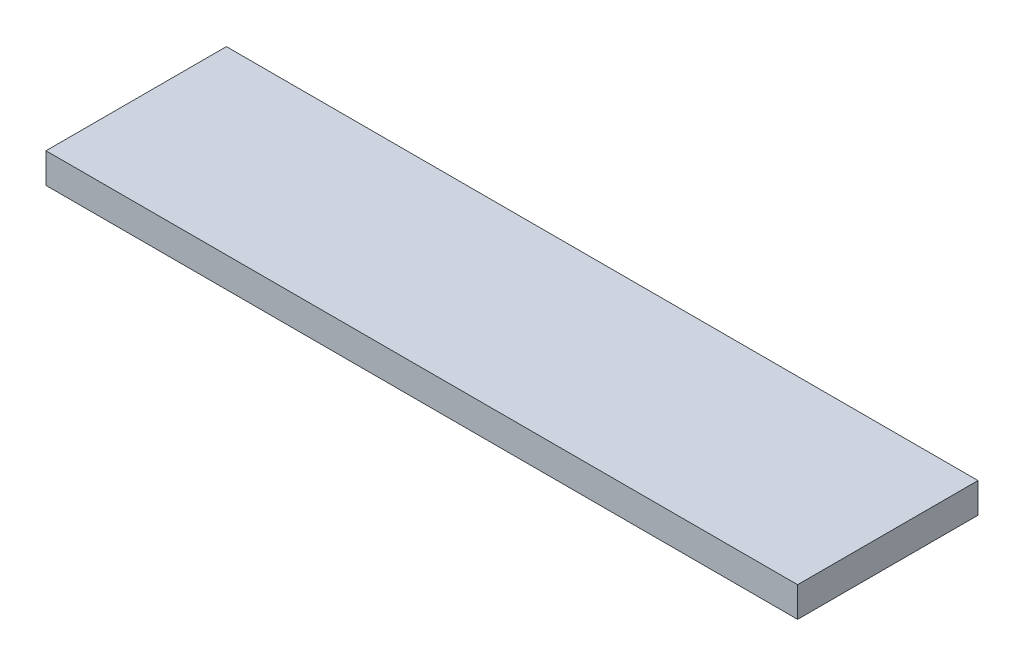
SolidWorks part; units mm, degrees
ref_plane "Front Plane" through (0, 0, 0) normal (0, 0, 1) x (1, 0, 0)
ref_plane "Top Plane" through (0, 0, 0) normal (0, 1, 0) x (1, 0, 0)
ref_plane "Right Plane" through (0, 0, 0) normal (1, 0, 0) x (0, 0, -1)
sketch "Sketch1" plane through (0, 0, 0) normal (0, 1, 0) x (1, 0, 0)
  line L1 (-62.5, 15) -> (62.5, 15)
  line L2 (-62.5, 15) -> (-62.5, -15)
  line L3 (-62.5, -15) -> (62.5, -15)
  line L4 (62.5, 15) -> (62.5, -15)
  line L5 (-62.5, 15) -> (62.5, -15) construction
  line L6 (-62.5, -15) -> (62.5, 15) construction
  point P0 (0, 0)
  dimension "D1" = 30
  dimension "D2" = 125
extrude "Boss-Extrude1" add sketch "Sketch1" along normal blind 5
